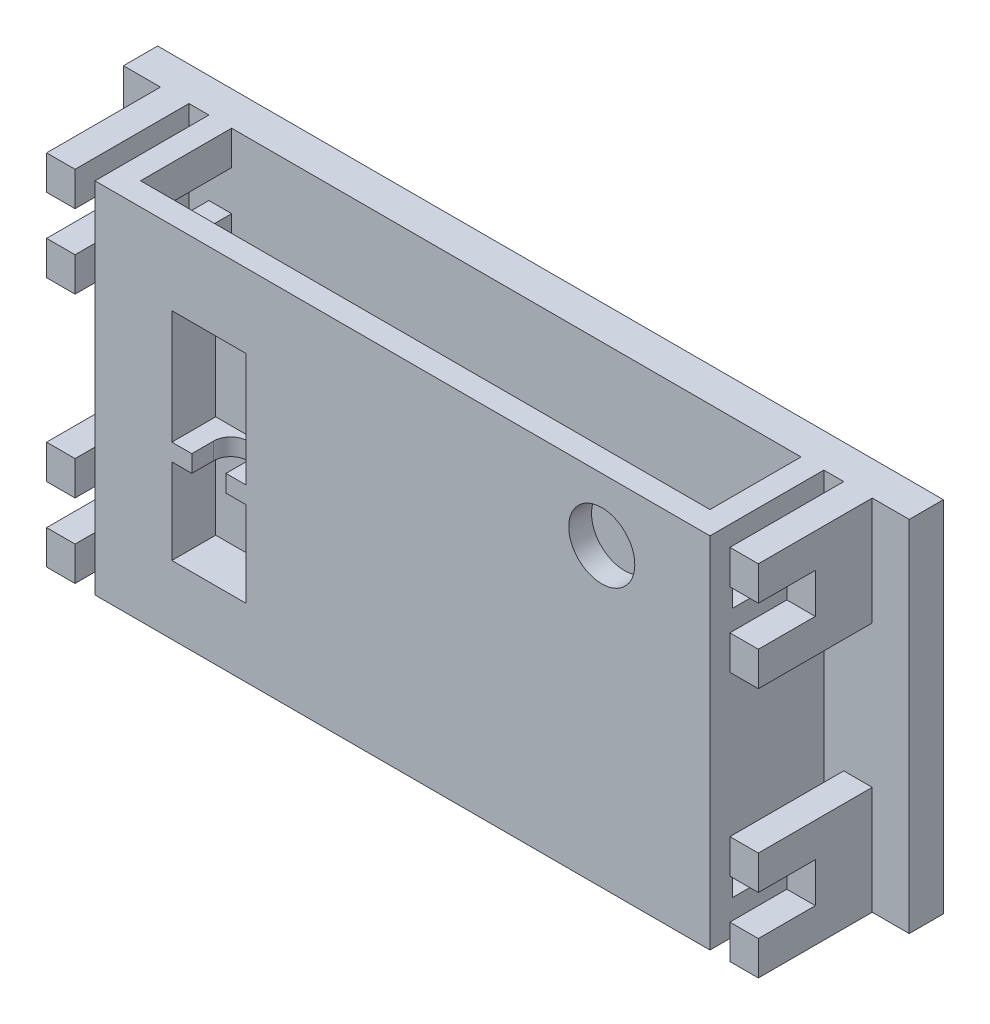
SolidWorks part; units mm, degrees
ref_plane "Plano frontal" through (0, 0, 0) normal (0, 0, 1) x (1, 0, 0)
ref_plane "Plano superior" through (0, 0, 0) normal (0, 1, 0) x (1, 0, 0)
ref_plane "Plano direito" through (0, 0, 0) normal (1, 0, 0) x (0, 0, -1)
sketch "Esboço1" plane through (0, 0, 0) normal (0, 0, 1) x (1, 0, 0)
  line L0 (0, -31.682) -> (0, -0.182)
  line L1 (0, -31.682) -> (-69, -31.682)
  line L3 (0, -0.182) -> (-69, -0.182)
  line L4 (-69, -31.682) -> (-69, -0.182)
  point P0 (0, 0)
  dimension "D1" = 31.5
  dimension "D2" = 69
extrude "Ressalto-extrusão1" add sketch "Esboço1" along normal blind 6
sketch "Esboço2" plane through (0, 0, 6) normal (0, 0, 1) x (1, 0, 0)
  line L0 (-69, -31.682) -> (0, -31.682) construction
  line L1 (-62.5, -31.682) -> (-57.5, -31.682)
  line L2 (-62.5, -31.682) -> (-62.5, -12.682)
  line L3 (-62.5, -12.682) -> (-57.5, -12.682)
  line L4 (-57.5, -31.682) -> (-57.5, -12.682)
  line L5 (-69, -0.182) -> (-69, -31.682) construction
  dimension "D1" = 19
  dimension "D2" = 5
  dimension "D3" = 6.5
extrude "Ressalto-extrusão2" add sketch "Esboço2" along normal blind 20
sketch "Esboço3" plane through (0, 0, 26) normal (0, 0, 1) x (1, 0, 0)
  line L0 (-57.5, -31.682) -> (-57.5, -12.682) construction
  line L1 (-57.5, -18.682) -> (-62.5, -18.682)
  line L2 (-57.5, -18.682) -> (-57.5, -25.682)
  line L3 (-57.5, -25.682) -> (-62.5, -25.682)
  line L4 (-62.5, -18.682) -> (-62.5, -25.682)
  line L5 (-62.5, -12.682) -> (-62.5, -31.682) construction
  line L6 (-57.5, -12.682) -> (-62.5, -12.682) construction
  line L7 (-62.5, -31.682) -> (-57.5, -31.682) construction
  dimension "D1" = 6
  dimension "D2" = 6
extrude "Corte-extrusão1" cut sketch "Esboço3" against normal blind 10
sketch "Esboço4" plane through (0, 0, 6) normal (0, 0, 1) x (1, 0, 0)
  line L0 (-57.5, -31.682) -> (0, -31.682) construction
  line L1 (-54, -31.682) -> (-50, -31.682)
  line L2 (-54, -31.682) -> (-54, -0.182)
  line L3 (-54, -0.182) -> (-50, -0.182)
  line L4 (-50, -31.682) -> (-50, -0.182)
  line L5 (0, -0.182) -> (-69, -0.182) construction
  line L6 (-57.5, -31.682) -> (-57.5, -12.682) construction
  dimension "D1" = 3.5
  dimension "D2" = 4
extrude "Ressalto-extrusão3" add sketch "Esboço4" along normal blind 20
sketch "Esboço5" plane through (-50, 0, 0) normal (1, 0, 0) x (0, 0, -1)
  line L0 (-16, -25.682) -> (-6, -25.682)
  line L2 (-22, -18.682) -> (-22, -6.182)
  line L5 (-16, -18.682) -> (-6, -18.682)
  line L6 (-22, -6.182) -> (-22, -0.182)
  line L7 (-26, -0.182) -> (-6, -0.182) construction
  line L10 (-26, -31.682) -> (-26, -0.182) construction
  line L11 (-22, -18.682) -> (-22, -25.682)
  line L12 (-6, -31.682) -> (-6, -0.182) construction
  line L13 (-6, -25.682) -> (-6, -18.682)
  line L20 (-16, -18.682) -> (-16, -25.682)
  line L21 (-16, -25.682) -> (-26, -25.682)
  line L22 (-26, -25.682) -> (-26, -31.682)
  line L23 (-26, -31.682) -> (-6, -31.682)
  line L24 (-6, -31.682) -> (-6, -12.682)
  line L25 (-6, -12.682) -> (-26, -12.682)
  line L26 (-26, -12.682) -> (-26, -18.682)
  line L27 (-26, -18.682) -> (-16, -18.682)
  line L29 (-16, -25.682) -> (-22, -25.682)
  line L32 (-6, -25.682) -> (-6, -18.682)
  line L35 (-22, -18.682) -> (-16, -18.682)
  line M8 (-6, -31.682) -> (-6, -0.182)
  dimension "D1" = 4
  dimension "D2" = 0
extrude "Corte-extrusão2" cut sketch "Esboço5" against normal up to surface (4 mm away) contours L35 L11 L29 L0 L5 M8 region at (-50, -22.182, 11) region at (-50, -22.182, 19) up to face at (-54, -15.932, 16)
sketch "Esboço6" plane through (-50, 0, 0) normal (1, 0, 0) x (0, 0, -1)
  line L0 (-26, -31.682) -> (-26, -0.182) construction
  line L1 (-26, -31.682) -> (-22, -31.682)
  line L2 (-26, -31.682) -> (-26, -0.182)
  line L5 (-22, -31.682) -> (-22, -0.182)
  line L6 (-26, -0.182) -> (-6, -0.182) construction
  line L7 (-22, -0.182) -> (-26, -0.182)
  line L8 (-22, -18.682) -> (-22, -25.682) construction
extrude "Ressalto-extrusão4" add sketch "Esboço6" along normal up to surface (50 mm away) up to face at (0, -15.932, 3)
ref_plane "Plano2" through (0, -0.182, 0) normal (0, 1, 0) x (1, 0, 0)
mirror "Espelhar10" about plane through (0, -0.182, 0) normal (0, 1, 0) of bodies 110 103
ref_plane "Plano1" through (0, 0, 0) normal (1, 0, 0) x (0, 0, -1)
mirror "Espelhar11" about plane through (0, 0, 0) normal (1, 0, 0) of bodies 106
sketch "Esboço18" plane through (-54, 0, 0) normal (-1, 0, 0) x (0, 0, 1)
  line L0 (6, -31.682) -> (26, 31.318) construction
  line L1 (6, 31.318) -> (26, -31.682) construction
  line L12 (6, -18.682) -> (22, -18.682)
  line L13 (22, -18.682) -> (22, -25.682)
  line L14 (22, -25.682) -> (6, -25.682)
  line L15 (6, -25.682) -> (6, -31.682)
  line L16 (6, -31.682) -> (26, -31.682)
  line L17 (26, -31.682) -> (26, 31.318)
  line L18 (26, 31.318) -> (6, 31.318)
  line L19 (6, 31.318) -> (6, 25.318)
  line L20 (6, 25.318) -> (22, 25.318)
  line L21 (22, 25.318) -> (22, 18.318)
  line L22 (22, 18.318) -> (6, 18.318)
  line L23 (6, 18.318) -> (6, -18.682)
  line L24 (6, -18.682) -> (22, -18.682)
  line L25 (22, -18.682) -> (22, -25.682)
  line L26 (22, -25.682) -> (6, -25.682)
  line L27 (6, -25.682) -> (6, -31.682)
  line L28 (6, -31.682) -> (26, -31.682)
  line L29 (26, -31.682) -> (26, 31.318)
  line L30 (26, 31.318) -> (6, 31.318)
  line L31 (6, 31.318) -> (6, 25.318)
  line L32 (6, 25.318) -> (22, 25.318)
  line L33 (22, 25.318) -> (22, 18.318)
  line L34 (22, 18.318) -> (6, 18.318)
  line L35 (6, 18.318) -> (6, -18.682)
  circle A0 centre (16, -0.182) radius 3.8
  point P14 (0, 0)
  dimension "D2" = 7.6
  dimension "D1" = 0
extrude "Corte-extrusão3" cut sketch "Esboço18" against normal up to surface (4 mm away) contours A0 region at (-54, -0.182, 16) up to face at (-50, -0.182, 14)
sketch "Esboço19" plane through (0, 0, 26) normal (0, 0, 1) x (1, 0, 0)
  line L0 (20, -31.682) -> (50, -31.682)
  line L7 (50, -31.682) -> (20, -31.682)
  line L8 (50, -31.682) -> (50, 31.318)
  line L9 (50, 31.318) -> (20, 31.318)
  line L10 (20, -31.682) -> (20, 31.318)
  line L11 (35, -31.682) -> (35, 31.318) construction
  line L13 (20, 20.318) -> (50, 20.318) construction
  line L20 (-54, -18.682) -> (-54, -25.682)
  line L21 (-50, -18.682) -> (-54, -18.682)
  line L22 (-50, 18.318) -> (-50, -18.682)
  line L23 (-54, 18.318) -> (-50, 18.318)
  line L24 (-54, 25.318) -> (-54, 18.318)
  line L25 (-50, 25.318) -> (-54, 25.318)
  line L26 (-50, 31.318) -> (-50, 25.318)
  line L27 (50, 31.318) -> (-50, 31.318)
  line L28 (50, 25.318) -> (50, 31.318)
  line L29 (54, 25.318) -> (50, 25.318)
  line L30 (54, 18.318) -> (54, 25.318)
  line L31 (50, 18.318) -> (54, 18.318)
  line L32 (50, -18.682) -> (50, 18.318)
  line L33 (54, -18.682) -> (50, -18.682)
  line L34 (54, -25.682) -> (54, -18.682)
  line L35 (50, -25.682) -> (54, -25.682)
  line L36 (50, -31.682) -> (50, -25.682)
  line L37 (-50, -31.682) -> (50, -31.682)
  line L38 (-50, -25.682) -> (-50, -31.682)
  line L39 (-54, -25.682) -> (-50, -25.682)
  line L47 (50, 31.318) -> (-50, 31.318)
  line L48 (50, 25.318) -> (50, 31.318)
  line L49 (54, 25.318) -> (50, 25.318)
  line L50 (54, 18.318) -> (54, 25.318)
  line L51 (50, 18.318) -> (54, 18.318)
  line L52 (50, -18.682) -> (50, 18.318)
  line L53 (54, -18.682) -> (50, -18.682)
  line L54 (54, -25.682) -> (54, -18.682)
  line L55 (50, -25.682) -> (54, -25.682)
  line L56 (50, -31.682) -> (50, -25.682)
  line L57 (-50, -31.682) -> (50, -31.682)
  circle A1 centre (35, 20.318) radius 5.8
  dimension "D7" = 11.6
  dimension "D5" = 30
  dimension "D6" = 11
  dimension "D1" = 0
extrude "Corte-extrusão5" cut sketch "Esboço19" against normal up to surface (4 mm away) contours A1 region at (35, 20.318, 26) up to face at (0, -0.182, 22)
sketch "Esboço20" plane through (0, 0, 22) normal (0, 0, -1) x (-1, 0, 0)
  line L0 (34, 22.318) -> (34, 31.318) construction
  line L5 (24, 22.318) -> (44, 22.318)
  line L6 (24, 22.318) -> (24, -22.682)
  line L7 (24, -22.682) -> (44, -22.682)
  line L8 (44, 22.318) -> (44, -22.682)
  line L10 (34, -22.682) -> (34, -31.682) construction
  line L20 (54, -25.682) -> (54, -18.682)
  line L21 (54, -18.682) -> (50, -18.682)
  line L22 (50, -18.682) -> (50, 18.318)
  line L23 (50, 18.318) -> (54, 18.318)
  line L24 (54, 18.318) -> (54, 25.318)
  line L25 (54, 25.318) -> (50, 25.318)
  line L26 (50, 25.318) -> (50, 31.318)
  line L27 (50, 31.318) -> (-50, 31.318)
  line L28 (-50, 31.318) -> (-50, 25.318)
  line L29 (-50, 25.318) -> (-54, 25.318)
  line L30 (-54, 25.318) -> (-54, 18.318)
  line L31 (-54, 18.318) -> (-50, 18.318)
  line L32 (-50, 18.318) -> (-50, -18.682)
  line L33 (-50, -18.682) -> (-54, -18.682)
  line L34 (-54, -18.682) -> (-54, -25.682)
  line L35 (-54, -25.682) -> (-50, -25.682)
  line L36 (-50, -25.682) -> (-50, -31.682)
  line L37 (-50, -31.682) -> (50, -31.682)
  line L38 (50, -31.682) -> (50, -25.682)
  line L39 (50, -25.682) -> (54, -25.682)
  line L40 (54, -25.682) -> (54, -18.682)
  line L41 (54, -18.682) -> (50, -18.682)
  line L42 (50, -18.682) -> (50, 18.318)
  line L43 (50, 18.318) -> (54, 18.318)
  line L44 (54, 18.318) -> (54, 25.318)
  line L45 (54, 25.318) -> (50, 25.318)
  line L46 (50, 25.318) -> (50, 31.318)
  line L47 (50, 31.318) -> (-50, 31.318)
  line L48 (-50, 31.318) -> (-50, 25.318)
  line L49 (-50, 25.318) -> (-54, 25.318)
  line L50 (-54, 25.318) -> (-54, 18.318)
  line L51 (-54, 18.318) -> (-50, 18.318)
  line L52 (-50, 18.318) -> (-50, -18.682)
  line L53 (-50, -18.682) -> (-54, -18.682)
  line L54 (-54, -18.682) -> (-54, -25.682)
  line L55 (-54, -25.682) -> (-50, -25.682)
  line L56 (-50, -25.682) -> (-50, -31.682)
  line L57 (-50, -31.682) -> (50, -31.682)
  line L58 (50, -31.682) -> (50, -25.682)
  line L59 (50, -25.682) -> (54, -25.682)
  dimension "D2" = 45
  dimension "D3" = 20
  dimension "D4" = 6
  dimension "D1" = 0
extrude "Ressalto-extrusão9" add sketch "Esboço20" along normal blind 7 contours L8 L5 L6 L7 region at (-34, -0.182, 22)
sketch "Esboço21" plane through (0, 0, 26) normal (0, 0, 1) x (1, 0, 0)
  line L0 (-40.5, -12.182) -> (-44, -12.182) construction
  line L1 (-40.5, -19.682) -> (-27.5, -19.682)
  line L2 (-40.5, -19.682) -> (-40.5, -4.682)
  line L3 (-40.5, -4.682) -> (-27.5, -4.682)
  line L4 (-44, 22.318) -> (-44, -22.682)
  line L5 (-24, 22.318) -> (-44, 22.318)
  line L6 (-24, -22.682) -> (-24, 22.318)
  line L7 (-44, -22.682) -> (-24, -22.682)
  line L8 (-44, 22.318) -> (-44, -22.682)
  line L9 (-24, 22.318) -> (-44, 22.318)
  line L10 (-24, -22.682) -> (-24, 22.318)
  line L11 (-44, -22.682) -> (-24, -22.682)
  line L12 (-27.5, -19.682) -> (-27.5, -4.682)
  line L13 (-24, -12.182) -> (-27.5, -12.182) construction
  dimension "D2" = 13
  dimension "D3" = 15
  dimension "D4" = 3
  dimension "D1" = 0
extrude "Corte-extrusão6" cut sketch "Esboço21" against normal blind 7.7 contours L2 L1 L12 L3
sketch "Esboço22" plane through (0, 0, 26) normal (0, 0, 1) x (1, 0, 0)
  line L0 (-40.5, -19.682) -> (-40.5, -4.682) construction
  line L1 (-40.5, -1.682) -> (-27.5, -1.682)
  line L2 (-40.5, -1.682) -> (-40.5, 18.318)
  line L3 (-40.5, 18.318) -> (-27.5, 18.318)
  line L4 (-44, 22.318) -> (-44, -22.682)
  line L5 (-24, 22.318) -> (-44, 22.318)
  line L6 (-24, -22.682) -> (-24, 22.318)
  line L7 (-44, -22.682) -> (-24, -22.682)
  line L8 (-44, 22.318) -> (-44, -22.682)
  line L9 (-24, 22.318) -> (-44, 22.318)
  line L10 (-24, -22.682) -> (-24, 22.318)
  line L11 (-44, -22.682) -> (-24, -22.682)
  line L12 (-27.5, -1.682) -> (-27.5, 18.318)
  line L17 (-27.5, -4.682) -> (-40.5, -4.682)
  line L18 (-40.5, -4.682) -> (-40.5, -19.682)
  line L19 (-40.5, -19.682) -> (-27.5, -19.682)
  line L20 (-27.5, -19.682) -> (-27.5, -4.682)
  line L21 (-27.5, -4.682) -> (-40.5, -4.682)
  line L22 (-40.5, -4.682) -> (-40.5, -19.682)
  line L23 (-40.5, -19.682) -> (-27.5, -19.682)
  line L24 (-27.5, -19.682) -> (-27.5, -4.682)
  dimension "D2" = 20
  dimension "D3" = 13
  dimension "D5" = 3
  dimension "D1" = 0
  dimension "D4" = 0
extrude "Corte-extrusão7" cut sketch "Esboço22" against normal blind 7.7 contours L2 L1 L12 L3
sketch "Esboço23" plane through (0, -1.682, 0) normal (0, 1, 0) x (1, 0, 0)
  line L0 (-27.5, -26) -> (-40.5, -18.3) construction
  line L1 (-40.5, -26) -> (-27.5, -18.3) construction
  line L2 (-31, -22.15) -> (-27.5, -22.15)
  line L3 (-37, -22.15) -> (-40.5, -22.15)
  line L4 (-40.5, -26) -> (-27.5, -26)
  line L5 (-27.5, -26) -> (-27.5, -18.3)
  line L6 (-27.5, -18.3) -> (-40.5, -18.3)
  line L7 (-40.5, -18.3) -> (-40.5, -26)
  line L8 (-40.5, -26) -> (-27.5, -26)
  line L9 (-27.5, -26) -> (-27.5, -18.3)
  line L10 (-27.5, -18.3) -> (-40.5, -18.3)
  line L11 (-40.5, -18.3) -> (-40.5, -26)
  line L12 (-31, -22.15) -> (-31, -26)
  line L13 (-37, -22.15) -> (-37, -26)
  arc A0 (-31, -22.15) -> (-37, -22.15) centre (-34, -22.15) ccw
  point P10 (0, 0)
  point P13 (-31.0008, -22.15)
  point P14 (-37.0921, -22.15)
  dimension "D2" = 6
  dimension "D1" = 0
extrude "Corte-extrusão9" cut sketch "Esboço23" against normal up to surface (3 mm away) contours L12 A0 L13 L8 region at (-34, -1.682, 22.8608) up to face at (-34, -4.682, 22.15)
